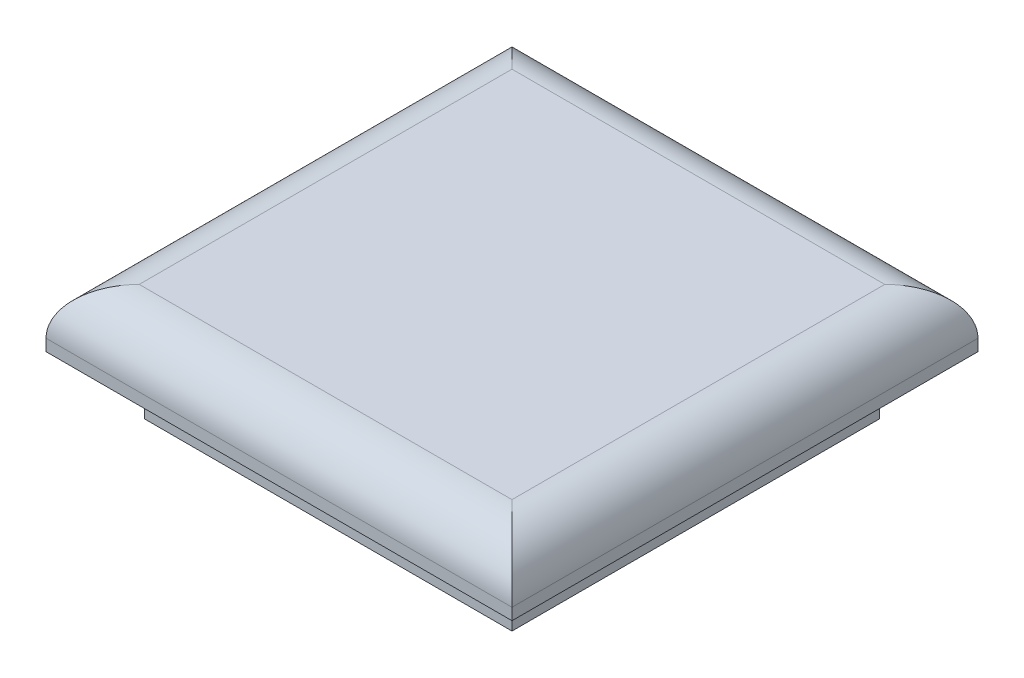
SolidWorks part; units mm, degrees
ref_plane "Front Plane" through (0, 0, 0) normal (0, 0, 1) x (1, 0, 0)
ref_plane "Top Plane" through (0, 0, 0) normal (0, 1, 0) x (1, 0, 0)
ref_plane "Right Plane" through (0, 0, 0) normal (1, 0, 0) x (0, 0, -1)
sketch "Sketch2" plane through (0, 0, 0) normal (0, 1, 0) x (1, 0, 0)
  line L0 (10.014, 20.028) -> (10.014, 0) construction
  line L1 (0, 0) -> (20.028, 0)
  line L2 (0, 0) -> (0, 20.028)
  line L3 (0, 20.028) -> (20.028, 20.028)
  line L4 (20.028, 0) -> (20.028, 20.028)
  line L5 (-2.686, 22.714) -> (22.714, 22.714)
  line L6 (-2.686, 22.714) -> (-2.686, -2.686)
  line L7 (-2.686, -2.686) -> (22.714, -2.686)
  line L8 (22.714, 22.714) -> (22.714, -2.686)
  line L9 (20.028, 10.014) -> (0, 10.014) construction
  line L10 (-2.686, 10.014) -> (22.714, 10.014) construction
  line L11 (10.014, -2.686) -> (10.014, 22.714) construction
  line L12 (3.175, 16.853) -> (16.853, 16.853)
  line L13 (16.853, 3.175) -> (16.853, 16.853)
  line L14 (3.175, 3.175) -> (16.853, 3.175)
  line L15 (3.175, 3.175) -> (3.175, 16.853)
  point P13 (-2.686, 10.014)
  point P14 (10.014, -2.686)
  point P15 (10.014, 22.714)
  point P16 (22.714, 10.014)
  dimension "D1" = 20.028
  dimension "D2" = 20.028
  dimension "D3" = 25.4
  dimension "D4" = 25.4
  dimension "D5" = 3.175
extrude "Boss-Extrude2" add sketch "Sketch2" against normal blind 3.175 contours L1 L4 L3 L2 L14 L15 L12 L13 region at (0.2832, 0, -10.014)
extrude "Boss-Extrude3" add sketch "Sketch2<3>" along normal blind 3.175 contours L1 L4 L3 L2 L14 L15 L12 L13 | L8 L5 L6 L7 L4 L1 L2 L3 | L15 L14 L13 L12 region at (0.2832, 0, -10.014) region at (10.014, 0, -22.3548) region at (10.014, 0, -10.014)
sketch "Sketch2<3>" plane through (0, 0, 0) normal (0, 1, 0) x (1, 0, 0) same geometry as "Sketch2"
fillet "Fillet1" radius 2.54 4 edges at (10.014, 3.175, -22.714) (22.714, 3.175, -10.014) (10.014, 3.175, 2.686) (-2.686, 3.175, -10.014)
sketch "Sketch3" plane through (0, 0, 0) normal (0, 0, 1) x (1, 0, 0)
  line L0 (0, -0.4) -> (0.4, 0)
  line L1 (0, -3.175) -> (0, 0) construction
  line L2 (-2.686, 0) -> (22.714, 0) construction
  line L3 (0.4, 0) -> (0, 0)
  line L4 (0, 0) -> (0, -0.4)
  line L5 (10.014, 0) -> (10.014, -3.175) construction
  line L6 (0, 0) -> (20.028, 0) construction
  line L7 (0, -3.175) -> (20.028, -3.175) construction
  line L8 (20.028, -0.4) -> (19.628, 0)
  line L9 (19.628, 0) -> (20.028, 0)
  line L10 (20.028, 0) -> (20.028, -0.4)
  dimension "D1" = 0.4
  dimension "D2" = 0.4
extrude "Cut-Extrude1" cut sketch "Sketch3" against normal through all
